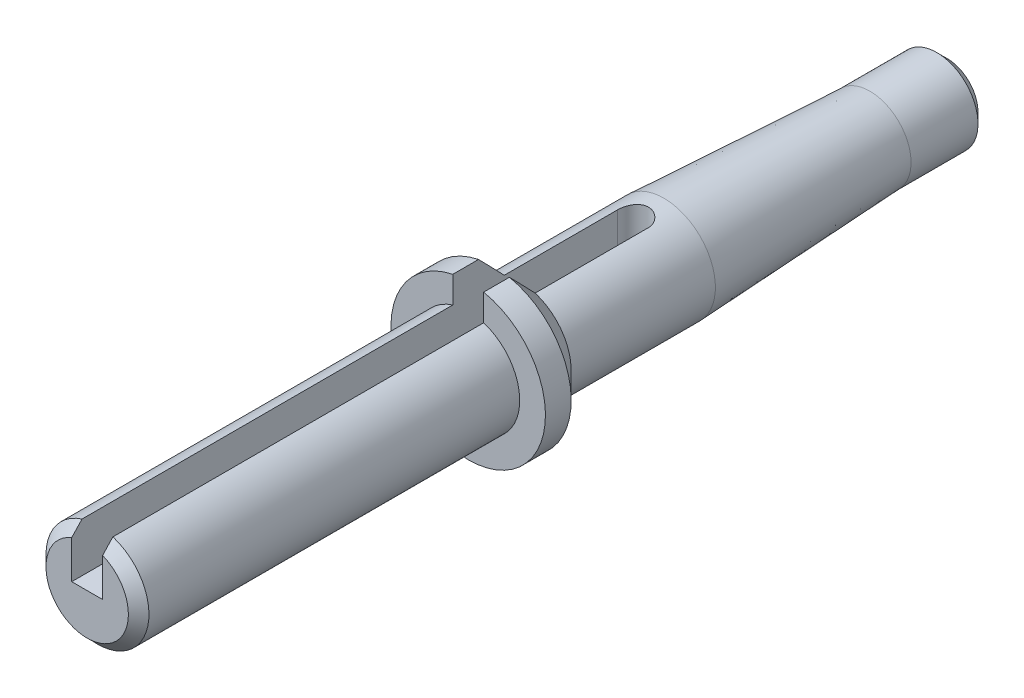
SolidWorks part; units mm, degrees
material "Ст20"
ref_plane "Front Plane" through (0, 0, 0) normal (0, 0, 1) x (1, 0, 0)
ref_plane "Top Plane" through (0, 0, 0) normal (0, 1, 0) x (1, 0, 0)
ref_plane "Right Plane" through (0, 0, 0) normal (1, 0, 0) x (0, 0, -1)
sketch "Sketch1" plane through (0, 0, 0) normal (0, 0, 1) x (1, 0, 0)
  circle A0 centre (0, 0) radius 5
extrude "Boss-Extrude1" add sketch "Sketch1" along normal blind 16.5
sketch "Sketch2" plane through (0, 0, 16.5) normal (0, 0, 1) x (1, 0, 0)
  circle A0 centre (0, 0) radius 7.5
extrude "Boss-Extrude2" add sketch "Sketch2" along normal blind 39.5
ref_plane "Plane4" through (0, 0, -21) normal (0, 0, -1) x (-1, 0, 0)
ref_plane "Plane5" through (0, 0, 0) normal (0, 0, -1) x (-1, 0, 0)
sketch "Sketch9" plane through (0, 0, 0) normal (0, 0, -1) x (-1, 0, 0)
  circle A0 centre (0, 0) radius 5
ref_axis "Axis5" through (0, 0, 56) along (0, 0, -1)
sketch "Sketch16" plane through (0, 0, 0) normal (0, 1, 0) x (1, 0, 0)
  line L1 (8, -19) -> (5, -19)
  line L2 (8, -19) -> (8, -83.5)
  line L3 (8, -83.5) -> (5, -83.5)
  line L4 (5, -19) -> (5, -83.5)
  dimension "D1" = 2.5
revolve "Cut-Revolve1" cut sketch "Sketch16" angle 360 about axis through (0, 0, 56) along (0, 0, -1)
cosmetic thread "Условное изображение резьбы2" parameters "D1"=19, "D2"=8.344
sketch "Sketch38" plane through (0, 0, 0) normal (0, 1, 0) x (1, 0, 0)
  line L0 (7.5, -16.5) -> (-7.5, -16.5) construction
  line L1 (0, 0) -> (0, -16.5) construction
  line L4 (-1.5, -3) -> (-1.5, -67.2439)
  line L6 (1.5, -3) -> (1.5, -67.2439)
  arc A0 (-1.5, -3) -> (1.5, -3) centre (0, -3) cw
  arc A1 (-1.5, -67.2439) -> (1.5, -67.2439) centre (0, -67.2439) ccw
  point P0 (0, -1.5)
  point P1 (0, 0)
  dimension "D2" = 3
  dimension "D3" = 3
chamfer "Фаска1" distance 2.5 angle 45 1 edges at (5, 0, 16.5)
extrude "Бобышка-Вытянуть1" add sketch "Sketch9" along normal blind 20 draft 2.863
sketch "Эскиз1" plane through (0, 0, -20) normal (0, 0, -1) x (-1, 0, 0)
  circle A0 centre (0, 0) radius 4
extrude "Бобышка-Вытянуть2" add sketch "Эскиз1" along normal blind 7.5
cosmetic thread "Условное изображение резьбы3" parameters "D1"=7.5, "D2"=6.619
chamfer "Фаска2" distance 1 angle 45 2 edges at (5, 0, 56) (-4, 0, -27.5)
extrude "Вырез-Вытянуть1" cut sketch "Sketch38" along normal blind 10
